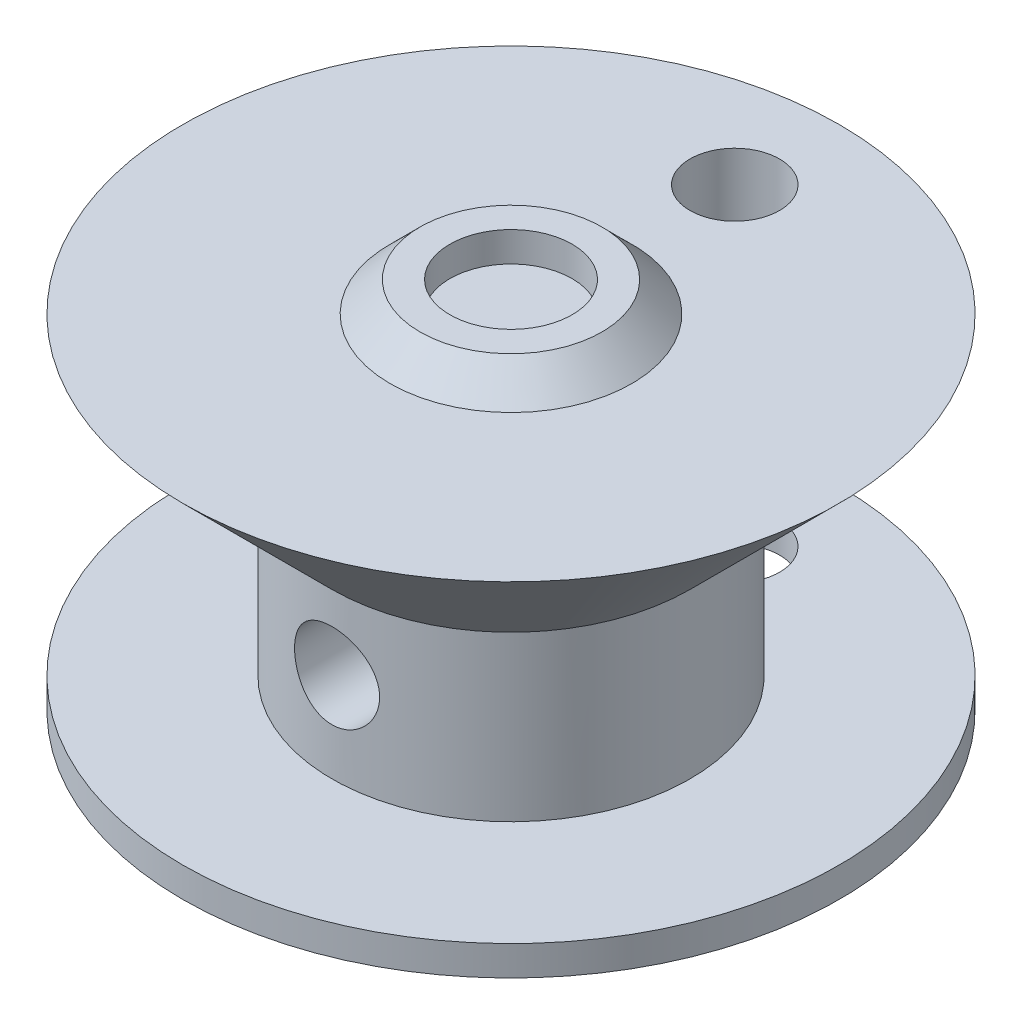
SolidWorks part; units mm, degrees
material "ABS"
ref_plane "Front Plane" through (0, 0, 0) normal (0, 0, 1) x (1, 0, 0)
ref_plane "Top Plane" through (0, 0, 0) normal (0, 1, 0) x (1, 0, 0)
ref_plane "Right Plane" through (0, 0, 0) normal (1, 0, 0) x (0, 0, -1)
sketch "Sketch1" plane through (0, 0, 0) normal (1, 0, 0) x (0, 0, -1)
  line L0 (0, 6.25) -> (-11, 6.25) construction
  line L1 (0, 0) -> (0, 18.3424) construction
  line L2 (-11, 6.25) -> (-11, -6.25) construction
  line L3 (-11, -6.25) -> (0, -6.25) construction
  line L4 (0, -6.25) -> (0, 6.25) construction
  line L5 (-11, 6.25) -> (-11, 5.25)
  line L7 (-6, 0.25) -> (-6, -5.25)
  line L9 (-11, -5.25) -> (-11, -6.25)
  line L10 (-11, -6.25) -> (0, -6.25) construction
  line L11 (0, -6.25) -> (0, 6.25) construction
  line L12 (0, 6.25) -> (-11, 6.25) construction
  line L13 (-11, 5.25) -> (-6, 0.25)
  line L14 (-6, 0.25) -> (-6, 6.25) construction
  line L15 (-11, -5.25) -> (-6, -5.25)
  line L16 (-11, 6.25) -> (-2.5, 6.25)
  line L17 (2.5, -6.25) -> (-2.5, -6.25) construction
  line L18 (2.5, -6.25) -> (2.5, 6.25) construction
  line L19 (2.5, 6.25) -> (-2.5, 6.25) construction
  line L20 (-2.5, -6.25) -> (-2.5, 6.25) construction
  line L21 (2.5, -6.25) -> (-2.5, 6.25) construction
  line L22 (2.5, 6.25) -> (-2.5, -6.25) construction
  line L23 (-2.05, 5.25) -> (2.05, 5.25) construction
  line L24 (-2.05, 5.25) -> (-2.05, 7.25) construction
  line L25 (-2.05, 7.25) -> (2.05, 7.25) construction
  line L26 (2.05, 5.25) -> (2.05, 7.25) construction
  line L27 (-2.05, 5.25) -> (2.05, 7.25) construction
  line L28 (-2.05, 7.25) -> (2.05, 5.25) construction
  line L30 (-2.05, 5.25) -> (0, 5.25)
  line L31 (0, 5.25) -> (0, -6.25) construction
  line L33 (-2.5, 1.75) -> (-2.5, -6.25)
  line L34 (-2.5, -6.25) -> (-11, -6.25)
  line L35 (-2.5, 1.75) -> (0, 4.25)
  line L36 (0, 4.25) -> (0, 5.25)
  line L37 (-2.05, 5.25) -> (-2.05, 6.25)
  line L38 (-2.05, 6.25) -> (-2.5, 6.25)
  point P3 (0, 0)
  point P16 (0, 0)
  dimension "D1" = 22
  dimension "D2" = 8
  dimension "D3" = 45
  dimension "D4" = 1
  dimension "D5" = 5
  dimension "D6" = 5
  dimension "D7" = 3.5
  dimension "D8" = 4.1
  dimension "D9" = 1
  dimension "D10" = 45
  dimension "D11" = 12
revolve "Spool Solid" add sketch "Sketch1" angle 360 about L1
sketch "Sketch2" plane through (0, -6.25, 0) normal (0, -1, 0) x (1, 0, 0)
  line L0 (1.5, 2) -> (-1.5, 2)
  circle A2 centre (0, 0) radius 2.5 construction
  circle A3 centre (0, 0) radius 2.5 construction
  arc A4 (1.5, 2) -> (-1.5, 2) centre (0, 0) ccw
  point P0 (0, -2.5)
  point P3 (0, 2)
  dimension "D1" = 4.5
extrude "Flatspot Extrude" add sketch "Sketch2" against normal up to next
sketch "Sketch5" plane through (0, -5.25, 0) normal (0, 1, 0) x (1, 0, 0)
  line L0 (0, 6) -> (0, 11) construction
  circle A0 centre (0, 7.5) radius 1.5
  circle A1 centre (0, 0) radius 6 construction
  circle A2 centre (0, 0) radius 11 construction
  dimension "D1" = 3
extrude "Wire Hole cut" cut sketch "Sketch5" against normal through all both and the other way through all
sketch "Sketch6" plane through (0, 0, 2) normal (0, 0, -1) x (-1, 0, 0)
  line L0 (0, -6.25) -> (0, 1.75) construction
  line L1 (1.5, -6.25) -> (-1.5, -6.25) construction
  circle A0 centre (0, -2.25) radius 1.425
  dimension "D2" = 2.85
  dimension "D1" = 8
extrude "Set Screw Cut" cut sketch "Sketch6" against normal through all
sketch "Sketch8" plane through (0, 6.25, 0) normal (0, 1, 0) x (1, 0, 0)
  circle A1 centre (0, 0) radius 11
  circle A4 centre (0, 0) radius 11 construction
  circle A5 centre (0, 0) radius 3.05
  circle A6 centre (0, 0) radius 3.05
  dimension "D1" = 1
extrude "Magnet Holder Trim" cut sketch "Sketch8" against normal blind 1
chamfer "Magnet Holder Chamfer" distance 1 angle 45 1 edges at (0, 5.25, 3.05)
sketch "Sketch9" plane through (0, -6.25, 0) normal (0, -1, 0) x (1, 0, 0)
  line L2 (1.5652, 2.2) -> (-1.5652, 2.2)
  line L3 (1.5652, 2.2) -> (-1.5652, 2.2)
  arc A2 (-1.5652, 2.2) -> (1.5652, 2.2) centre (0, 0) ccw
  arc A3 (-1.5652, 2.2) -> (1.5652, 2.2) centre (0, 0) ccw
  dimension "D1" = 0.2
extrude "Axle Tolerance Cut" cut sketch "Sketch9" against normal up to vertex (8 mm away) up to point (-1.5, 1.75, 2)
